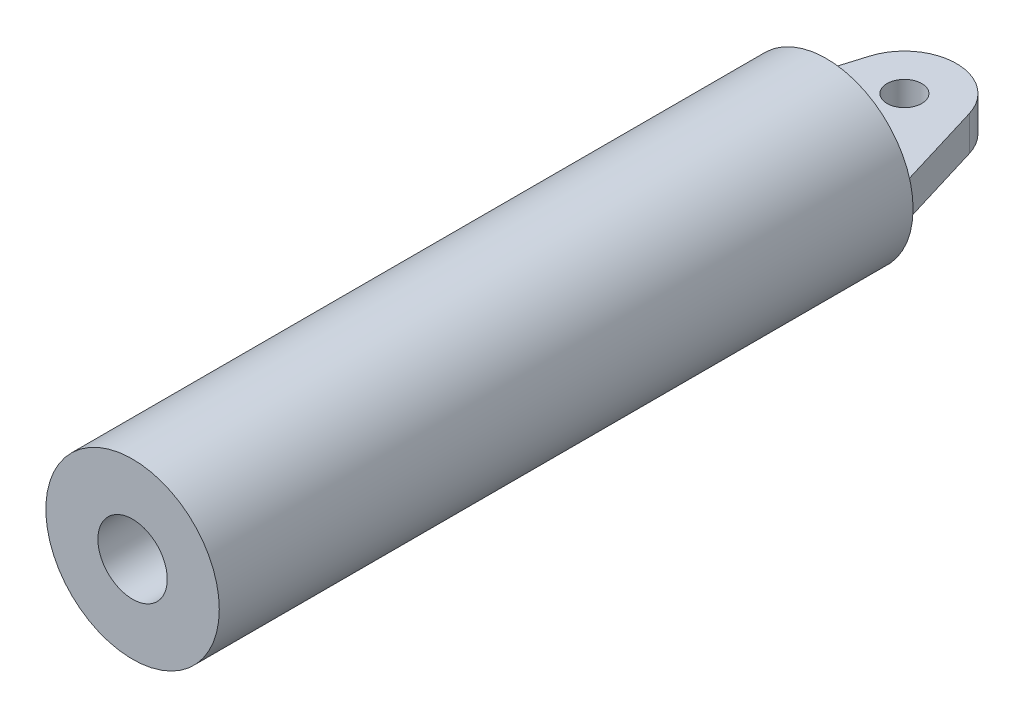
SolidWorks part; units mm, degrees
ref_plane "Front Plane" through (0, 0, 0) normal (0, 0, 1) x (1, 0, 0)
ref_plane "Top Plane" through (0, 0, 0) normal (0, 1, 0) x (1, 0, 0)
ref_plane "Right Plane" through (0, 0, 0) normal (1, 0, 0) x (0, 0, -1)
sketch "Sketch1" plane through (0, 0, 0) normal (0, 0, 1) x (1, 0, 0)
  circle A0 centre (0, 0) radius 50
  dimension "D1" = 100
extrude "Boss-Extrude1" add sketch "Sketch1" along normal blind 400
sketch "Sketch2" plane through (0, 0, 0) normal (0, 1, 0) x (1, 0, 0)
  line L0 (-45, 0) -> (-28.7083, 53.7083)
  line L1 (50, 0) -> (-50, 0) construction
  line L2 (28.7083, 53.7083) -> (45, 0)
  line L3 (-45, 0) -> (45, 0)
  circle A0 centre (0, 45) radius 10
  arc A1 (-28.7083, 53.7083) -> (28.7083, 53.7083) centre (0, 45) cw
  dimension "D1" = 20
  dimension "D2" = 30
  dimension "D3" = 45
  dimension "D4" = 45
  dimension "D5" = 45
extrude "Boss-Extrude2" add sketch "Sketch2" along normal mid plane 20
shell "Shell1" thickness 30 removed face at (50, 0, 400)
